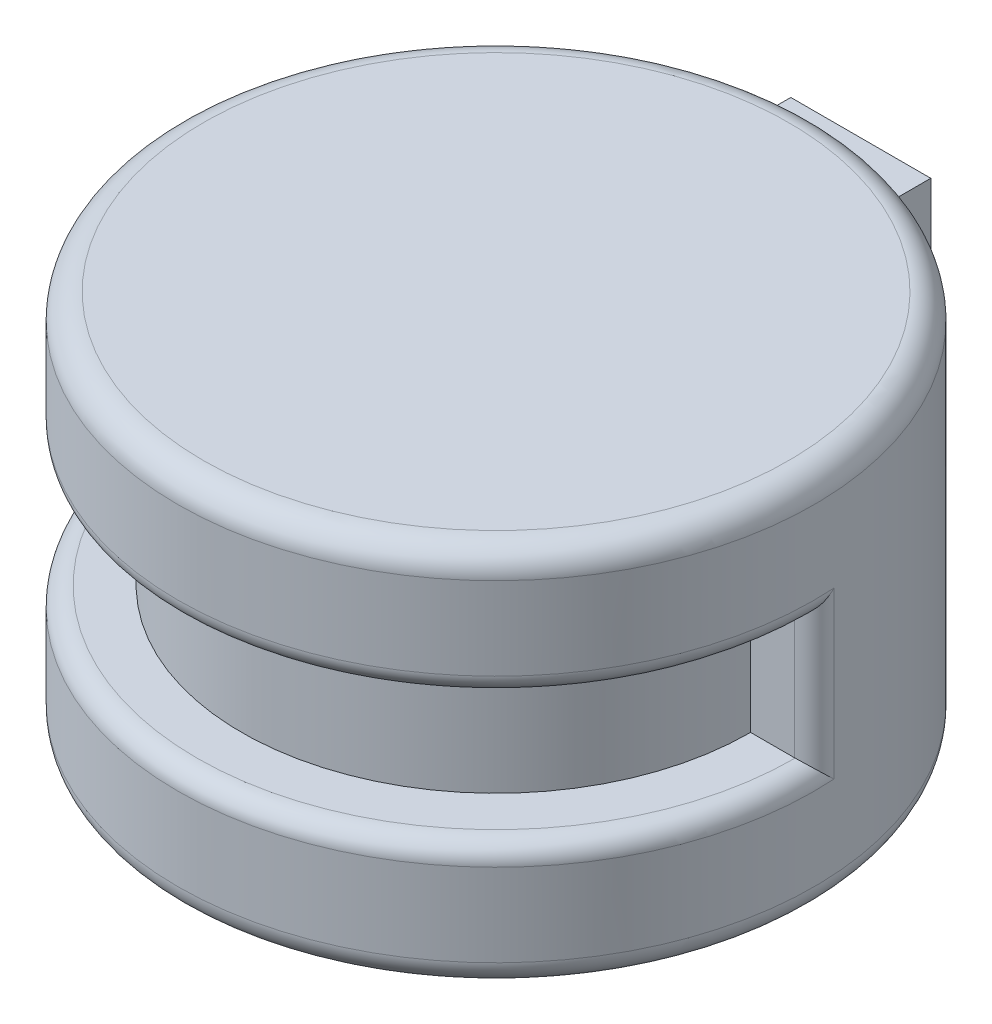
SolidWorks part; units mm, degrees
ref_plane "Front Plane" through (0, 0, 0) normal (0, 0, 1) x (1, 0, 0)
ref_plane "Top Plane" through (0, 0, 0) normal (0, 1, 0) x (1, 0, 0)
ref_plane "Right Plane" through (0, 0, 0) normal (1, 0, 0) x (0, 0, -1)
sketch "Sketch1" plane through (0, 0, 0) normal (0, 1, 0) x (1, 0, 0)
  line L0 (40, 0) -> (50, 0)
  line L1 (-40, 0) -> (-50, 0)
  circle A0 centre (0, 0) radius 50
  arc A1 (-40, 0) -> (40, 0) centre (0, 0) ccw
  dimension "D1" = 100
  dimension "D2" = 40
extrude "Boss-Extrude2" add sketch "Sketch1" against normal blind 60 contours L1 A1 L0 A0 region at (0, 0, -6.3144)
extrude "Boss-Extrude3" add sketch "Sketch1<4>" against normal blind 20 contours A1 L1 A0 L0 region at (45, 0, 1.118)
sketch "Sketch1<4>" plane through (0, 0, 0) normal (0, 1, 0) x (1, 0, 0) same geometry as "Sketch1"
extrude "Boss-Extrude5" add sketch "Sketch1<6>" against normal blind 20 from offset 40 contours A1 L1 A0 L0 region at (45, 0, 1.118) offset against normal yes
sketch "Sketch1<6>" plane through (0, 0, 0) normal (0, 1, 0) x (1, 0, 0) same geometry as "Sketch1"
fillet "Fillet1" radius 4 2 edges at (0, 0, 50) (0, -60, 50)
fillet "Fillet2" radius 3 4 edges at (-50, -30, 0) (50, -30, 0) (0, -20, 50) (0, -40, 50)
ref_plane "Plane1" through (0, 0, -50) normal (0, 0, 1) x (1, 0, 0)
sketch "Sketch2" plane through (0, 0, -50) normal (0, 0, 1) x (1, 0, 0)
  line L1 (-10.6851, -23.4211) -> (11.3149, -23.4211)
  line L2 (-10.6851, -23.4211) -> (-10.6851, -7.4211)
  line L3 (-10.6851, -7.4211) -> (11.3149, -7.4211)
  line L4 (11.3149, -23.4211) -> (11.3149, -7.4211)
  line L5 (-10.6851, -23.4211) -> (11.3149, -7.4211) construction
  line L6 (-10.6851, -7.4211) -> (11.3149, -23.4211) construction
  point P0 (0.3149, -15.4211)
  point P5 (0, -15.7899)
  dimension "D1" = 22
  dimension "D2" = 16
extrude "Boss-Extrude6" add sketch "Sketch2" along normal blind 5
extrude "Boss-Extrude7" add sketch "Sketch2<2>" against normal blind 7
sketch "Sketch2<2>" plane through (0, 0, -50) normal (0, 0, 1) x (1, 0, 0) same geometry as "Sketch2"
sketch "Sketch3" [suppressed] plane through (0, 0, -57) normal (0, 0, -1) x (-1, 0, 0)
  line L0 (-11.3149, -23.4211) -> (-11.3149, -7.4211) construction
  line L1 (10.6851, -23.4211) -> (-11.3149, -23.4211) construction
  circle A0 centre (-0.3149, -15.4211) radius 4
  point P0 (-0.3149, -15.4211)
  dimension "D3" = 8
  dimension "D1" = 11
  dimension "D2" = 8
scale "Scale6" scale about centroid uniform scaling yes scale factor 0.3
